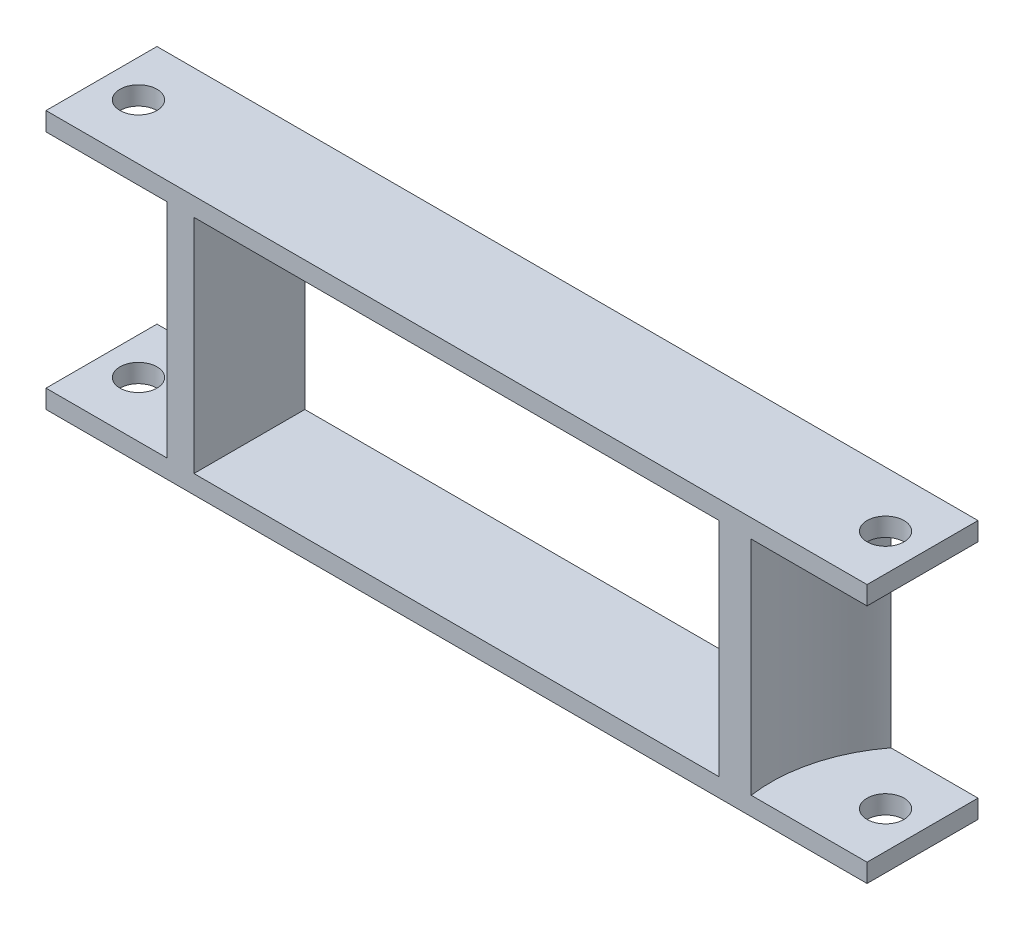
SolidWorks part; units mm, degrees
ref_plane "Alzado" through (0, 0, 0) normal (0, 0, 1) x (1, 0, 0)
ref_plane "Planta" through (0, 0, 0) normal (0, 1, 0) x (1, 0, 0)
ref_plane "Vista lateral" through (0, 0, 0) normal (1, 0, 0) x (0, 0, -1)
sketch "Croquis1" plane through (0, 0, 0) normal (0, 1, 0) x (1, 0, 0)
  line L1 (-36.106, -11.3281) -> (185.894, -11.3281)
  line L2 (-36.106, -11.3281) -> (-36.106, 18.6719)
  line L3 (-36.106, 18.6719) -> (185.894, 18.6719)
  line L4 (185.894, -11.3281) -> (185.894, 18.6719)
  circle A0 centre (-26.106, 3.6719) radius 5
  circle A1 centre (175.894, 3.6719) radius 5
  point P8 (0, 0)
  point P10 (-36.106, 1.0649)
  dimension "D3" = 10
  dimension "D4" = 10
  dimension "D5" = 15
  dimension "D1" = 30
  dimension "D2" = 222
  dimension "D6" = 10
  dimension "D7" = 10
  dimension "D8" = 15
extrude "Saliente-Extruir1" add sketch "Croquis1" along normal blind 70
ref_plane "Plano1" through (0, 35, 0) normal (0, -1, 0) x (-1, 0, 0)
sketch "Croquis2" plane through (0, 35, 0) normal (0, -1, 0) x (-1, 0, 0)
  circle A0 centre (42.3794, -2.3339) radius 40
  circle A1 centre (-194.158, -5.5815) radius 40
  dimension "D1" = 80
  dimension "D2" = 80
extrude "Cortar-Extruir1" cut sketch "Croquis2" against normal blind 30 and the other way blind 30
sketch "Croquis3" plane through (0, 0, 11.3281) normal (0, 0, 1) x (1, 0, 0)
  line L1 (3.894, 65) -> (145.894, 65)
  line L2 (3.894, 65) -> (3.894, 5)
  line L3 (3.894, 5) -> (145.894, 5)
  line L4 (145.894, 65) -> (145.894, 5)
  line L5 (-36.106, 0) -> (185.894, 0) construction
  line L6 (-36.106, 5) -> (-36.106, 0) construction
  dimension "D1" = 60
  dimension "D2" = 142
  dimension "D3" = 40
  dimension "D4" = 5
extrude "Cortar-Extruir2" cut sketch "Croquis3" against normal through all
ref_axis "z2" through (-26.106, 97.6337, -3.6719) along (0, -1, 0)
ref_axis "z3" through (175.894, 95.3058, -3.6719) along (0, -1, 0)
